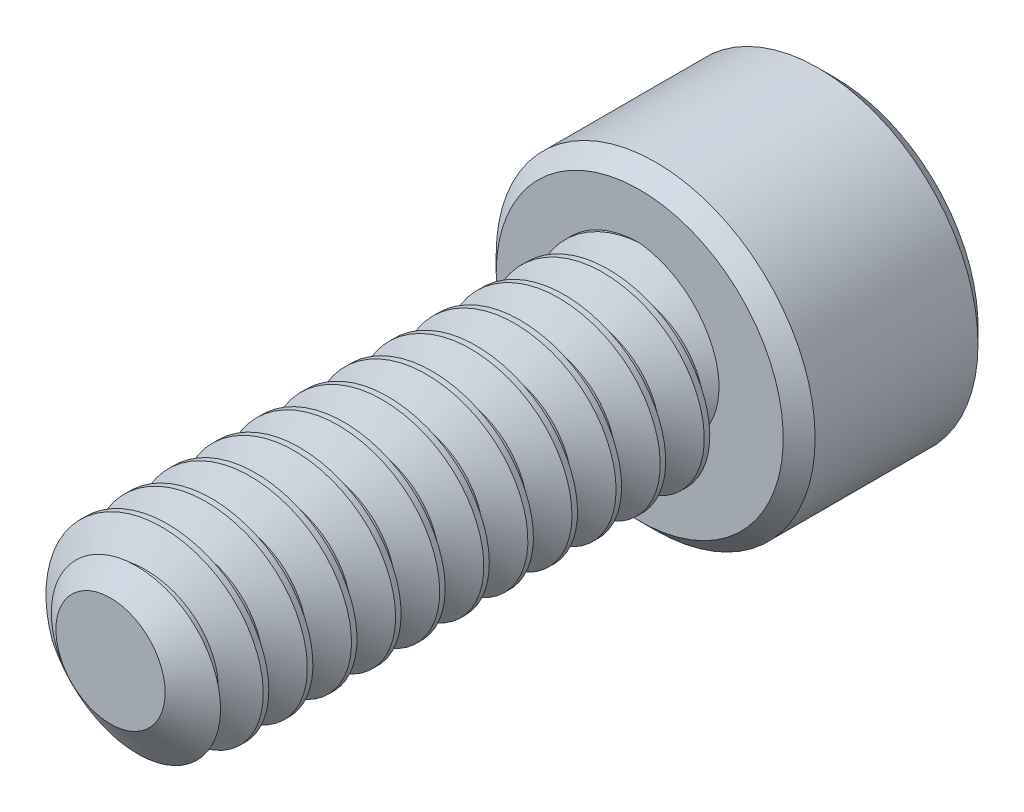
SolidWorks part; units mm, degrees
ref_plane "Front Plane" through (0, 0, 0) normal (0, 0, 1) x (1, 0, 0)
ref_plane "Top Plane" through (0, 0, 0) normal (0, 1, 0) x (1, 0, 0)
ref_plane "Right Plane" through (0, 0, 0) normal (1, 0, 0) x (0, 0, -1)
sketch "Sketch1" plane through (0, 0, 0) normal (0, 0, 1) x (1, 0, 0)
  circle A0 centre (0, 0) radius 1.7526
  dimension "OD" = 3.5052
extrude "Extrude1" add sketch "Sketch1" against normal blind 9.525
sketch "Sketch2" plane through (0, 0, 0) normal (0, 0, 1) x (1, 0, 0)
  circle A0 centre (0, 0) radius 1.7526 construction
  circle A1 centre (0, 0) radius 1.7526
curve "Helix/Spiral1" pitch 0.7937 height 10.3188 turns 13 parameters "pitch"=0.7937
sketch "Sketch3" plane through (0, 0, 0) normal (1, 0, 0) x (0, 0, -1)
  line L0 (-0.6945, 1.7526) -> (-0.3969, 1.237)
  line L1 (-0.3969, 1.237) -> (-0.2977, 1.237)
  line L2 (-0.2977, 1.237) -> (0, 1.7526)
  line L3 (-0.6945, 1.7526) -> (0, 1.7526)
  line L4 (-0.3473, 1.7526) -> (-0.3473, 1.237) construction
  line L5 (-0.5457, 1.4948) -> (-0.1488, 1.4948) construction
  line L6 (0, 1.7526) -> (0, -1.7526) construction
  dimension "D1" = 0.0992
  dimension "D2" = 0.3969
  dimension "D3" = 60
sweep "Cut-Sweep1" cut profiles "Sketch3" path "Helix/Spiral1"
sketch "Sketch4" plane through (0, 0, 0) normal (1, 0, 0) x (0, 0, -1)
  line L0 (0.5388, 1.7526) -> (0, 0.983)
  line L1 (0, 0.983) -> (0, 1.7526)
  line L2 (0.5388, 1.7526) -> (0, 1.7526)
  line L3 (-0.6945, 1.7526) -> (0, 1.7526) construction
  line L4 (0, 0) -> (7.0209, 0) construction
  dimension "D1" = 55
  dimension "D2" = 0.254
revolve "Cut-Revolve1" cut sketch "Sketch4" angle 360 about L4
sketch "Sketch6" plane through (0, 0, -9.525) normal (0, 0, -1) x (-1, 0, 0)
  circle A0 centre (0, 0) radius 2.8702
  dimension "head dia" = 5.7404
extrude "Extrude2" add sketch "Sketch6" along normal blind 3.5052
sketch "Sketch7" plane through (0, 0, -13.0302) normal (0, 0, -1) x (-1, 0, 0)
  line L1 (0, 1.604) -> (-1.3891, 0.802)
  line L2 (-1.3891, 0.802) -> (-1.3891, -0.802)
  line L3 (-1.3891, -0.802) -> (0, -1.604)
  line L4 (0, -1.604) -> (1.3891, -0.802)
  line L5 (1.3891, -0.802) -> (1.3891, 0.802)
  line L6 (1.3891, 0.802) -> (0, 1.604)
  circle A0 centre (0, 0) radius 1.3891 construction
  dimension "hex dia" = 2.7781
extrude "Cut-Extrude1" cut sketch "Sketch7" against normal blind 2.0836
sketch "Sketch8" plane through (0, 0, -13.0302) normal (0, 0, -1) x (-1, 0, 0)
  circle A0 centre (0, 0) radius 1.604
extrude "Cut-Extrude2" cut sketch "Sketch8" against normal through all draft 45
chamfer "Chamfer1" distance 0.287 angle 45 2 edges at (-2.8702, 0, -13.0302) (-2.8702, 0, -9.525)
sketch "Sketch10" plane through (0, 0, -9.525) normal (0, 0, 1) x (1, 0, 0)
  circle A1 centre (0, 0) radius 1.7526
  circle A2 centre (0, 0) radius 1.7526
  dimension "D1" = 0
ref_plane "Plane1" through (0, 0, -38.1) normal (0, 0, 1) x (1, 0, 0)
extrude "partial thread" [suppressed] add sketch "Sketch10" along normal up to surface (12.7 mm away) separate body
chamfer "Chamfer2" [suppressed] distance 0.0701 angle 45
combine bodies "Combine1" [suppressed] operation type add bodies to combine 107 108
sketch "Sketch9" plane through (0, 0, 0) normal (1, 0, 0) x (0, 0, -1)
  line L0 (0, 1.7526) -> (0, -1.7526) construction
  line L1 (1.9844, 1.7526) -> (1.9844, -1.7526) construction
  dimension "D1" = 1.9844
equation "\"D3@Helix/Spiral1\" = \"screw length@Extrude1\"+\"pitch@Helix/Spiral1\""
equation "\"D1@Sketch3\" = \"pitch@Helix/Spiral1\"*.125"
equation "\"D2@Sketch3\" = \"pitch@Helix/Spiral1\"*.5"
equation "\"D1@Cut-Extrude1\" = \"hex dia@Sketch7\"*.75"
equation "\"D1@Chamfer1\" = \"head dia@Sketch6\"*.05"
equation "\"D1@Sketch9\" = \"pitch@Helix/Spiral1\"*2.5"
equation "\"D1@Chamfer2\"=\"OD@Sketch1\"*.02"
